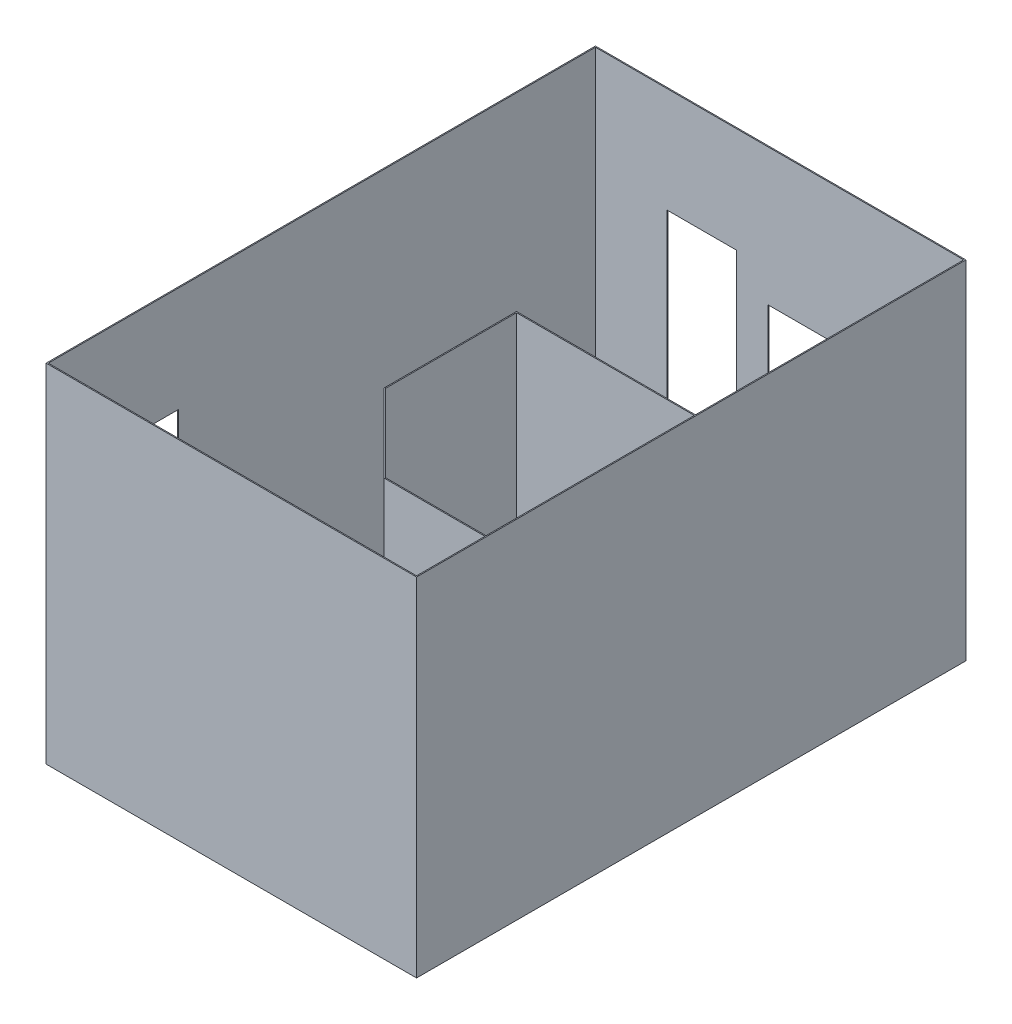
SolidWorks part; units mm, degrees
ref_plane "Спереди" through (0, 0, 0) normal (0, 0, 1) x (1, 0, 0)
ref_plane "Сверху" through (0, 0, 0) normal (0, 1, 0) x (1, 0, 0)
ref_plane "Справа" through (0, 0, 0) normal (1, 0, 0) x (0, 0, -1)
sketch "Эскиз1" plane through (0, 0, 0) normal (0, 1, 0) x (1, 0, 0)
  line L0 (0, 65) -> (-95.7538, 65)
  line L1 (0, 0) -> (-350, 0)
  line L2 (0, 0) -> (0, 520)
  line L3 (0, 520) -> (-350, 520)
  line L4 (-350, 0) -> (-350, 520)
  line L5 (-95.7538, 65) -> (-170, 139.2462)
  line L6 (-170, 139.2462) -> (-170, 265)
  line L7 (-170, 265) -> (0, 265)
  dimension "D1" = 520
  dimension "D2" = 350
  dimension "D3" = 135
  dimension "D4" = 65
  dimension "D5" = 200
  dimension "D6" = 170
  dimension "D7" = 105
extrude "Вытянуть-Тонкостенный2" add sketch "Эскиз1" along normal blind 330 thin thin type one direction wall 1
sketch "Эскиз2" plane through (0, 0, -521) normal (0, 0, -1) x (-1, 0, 0)
  line L0 (351, 330) -> (351, 0) construction
  line L1 (282, 10) -> (216, 10)
  line L2 (282, 10) -> (282, 230)
  line L3 (282, 230) -> (216, 230)
  line L4 (216, 10) -> (216, 230)
  line L5 (-1, 0) -> (351, 0) construction
  line L7 (186, 200) -> (32, 200)
  line L8 (186, 200) -> (186, 100)
  line L9 (186, 100) -> (32, 100)
  line L10 (32, 200) -> (32, 100)
  dimension "D1" = 69
  dimension "D2" = 66
  dimension "D3" = 10
  dimension "D4" = 220
  dimension "D5" = 154
  dimension "D6" = 100
  dimension "D7" = 30
  dimension "D8" = 100
extrude "Вырез-Вытянуть1" cut sketch "Эскиз2" against normal blind 10
sketch "Эскиз4" plane through (-15.3769, 0, 15.3769) normal (-0.7071, 0, 0.7071) x (0.7071, 0, 0.7071)
  line L0 (-113.6701, 0) -> (-218.6701, 0) construction
  line L1 (-198.6701, 220) -> (-133.6701, 220)
  line L2 (-198.6701, 220) -> (-198.6701, 0)
  line L3 (-198.6701, 0) -> (-133.6701, 0)
  line L4 (-133.6701, 220) -> (-133.6701, 0)
  line L5 (-218.6701, 330) -> (-218.6701, 0) construction
  dimension "D1" = 220
  dimension "D2" = 65
  dimension "D3" = 20
extrude "Вырез-Вытянуть2" cut sketch "Эскиз4" against normal blind 10
sketch "Эскиз5" plane through (-351, 0, 0) normal (-1, 0, 0) x (0, 0, 1)
  line L0 (1, 330) -> (1, 0) construction
  line L1 (-124, 230) -> (-42, 230)
  line L2 (-124, 230) -> (-124, 10)
  line L3 (-124, 10) -> (-42, 10)
  line L4 (-42, 230) -> (-42, 10)
  line L5 (-521, 0) -> (1, 0) construction
  dimension "D1" = 220
  dimension "D2" = 82
  dimension "D3" = 43
  dimension "D4" = 10
extrude "Вырез-Вытянуть3" cut sketch "Эскиз5" against normal blind 10
